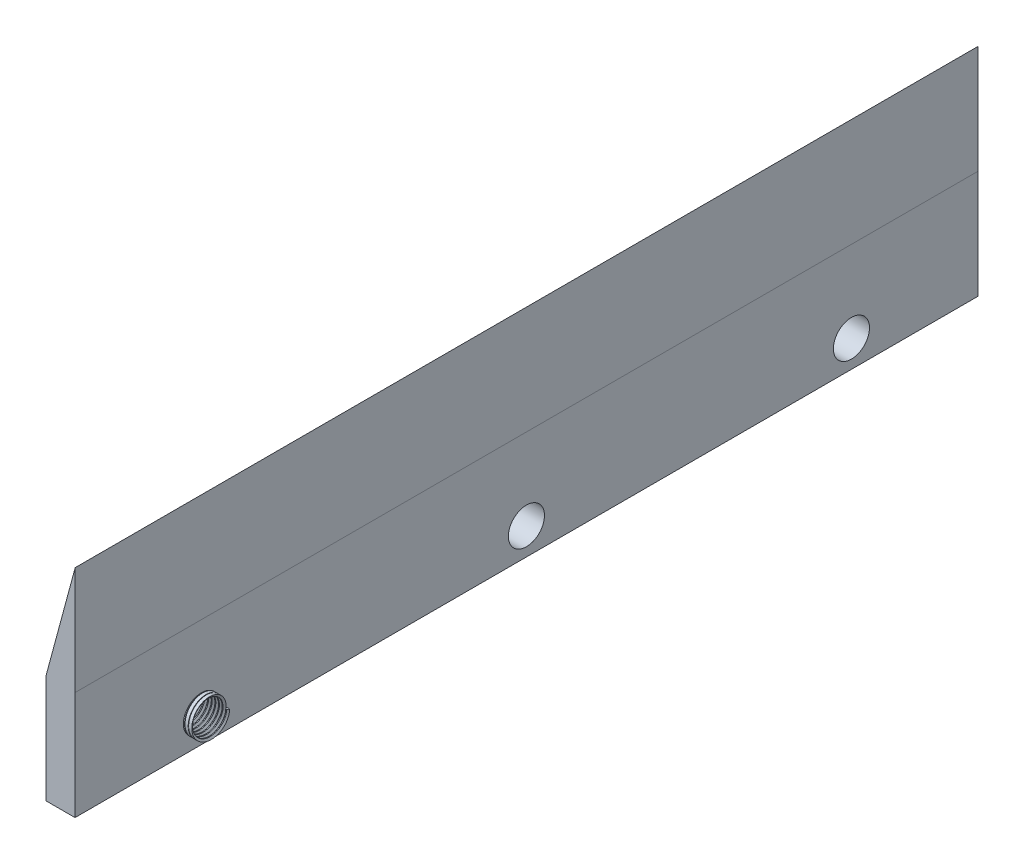
SolidWorks part; units mm, degrees
ref_plane "前基準面" through (0, 0, 0) normal (0, 0, 1) x (1, 0, 0)
ref_plane "上基準面" through (0, 0, 0) normal (0, 1, 0) x (1, 0, 0)
ref_plane "右基準面" through (0, 0, 0) normal (1, 0, 0) x (0, 0, -1)
sketch "草圖1" plane through (0, 0, 0) normal (0, 0, 1) x (1, 0, 0)
  line L0 (-16.4267, 183.61) -> (-24.4652, 183.61)
  line L1 (-24.4652, 183.61) -> (-24.4652, 213.61)
  line L4 (-16.3743, 243.596) -> (-24.4652, 213.61) construction
  line L5 (-16.3743, 243.596) -> (-24.4652, 213.61)
  line L6 (-16.3743, 243.596) -> (-16.4267, 213.596) construction
  line L7 (-16.3743, 243.596) -> (-16.4267, 213.596)
  line L8 (-16.4267, 213.596) -> (-16.4267, 183.61)
  dimension "D1" = 30
extrude "填料-伸長1" add sketch "草圖1" along normal blind 250
ref_plane "平面1" through (-24.4652, 0, 0) normal (1, 0, 0) x (0, 0, -1)
sketch "草圖2" plane through (-24.4652, 0, 0) normal (1, 0, 0) x (0, 0, -1)
  line L1 (0, 213.61) -> (0, 183.61) construction
  circle A0 centre (-215, 191.067) radius 5
  circle A1 centre (-125, 191.067) radius 5
  circle A2 centre (-35, 191.067) radius 5
  dimension "D1" = 10
  dimension "D2" = 10
  dimension "D3" = 10
  dimension "D4" = 90
  dimension "D5" = 90
  dimension "D6" = 35
extrude "除料-伸長1" cut sketch "草圖2" along normal through all
thread "螺紋1" pitch 1 method extrude profile "螺紋輪廓1" start angle 0, offset 0, length 10, pitch 1, diameter 10
ref_plane "平面2" through (-24.4652, 191.067, 210) normal (0, -1, 0) x (0, 0, -1)
sketch "螺紋輪廓1" plane through (-24.4652, 191.067, 210) normal (0, -1, 0) x (0, 0, -1)
  line L0 (0, 0) -> (0, 1) construction
  line L11 (0, 0) -> (0, 0.875)
  line L12 (0, 0.875) -> (-0.5413, 0.5625)
  line L13 (-0.5413, 0.5625) -> (-0.5413, 0.3125)
  line L15 (-0.5413, 0.3125) -> (0, 0)
  line L17 (-0.5413, 0.4375) -> (0, 0.4375) construction
  point P2 (0, 0)
  dimension "Pitch" = 1
  dimension "Profile_Angle" = 60
  dimension "Profile_Land" = 0.25
  dimension "Profile_Height" = 0.5413
